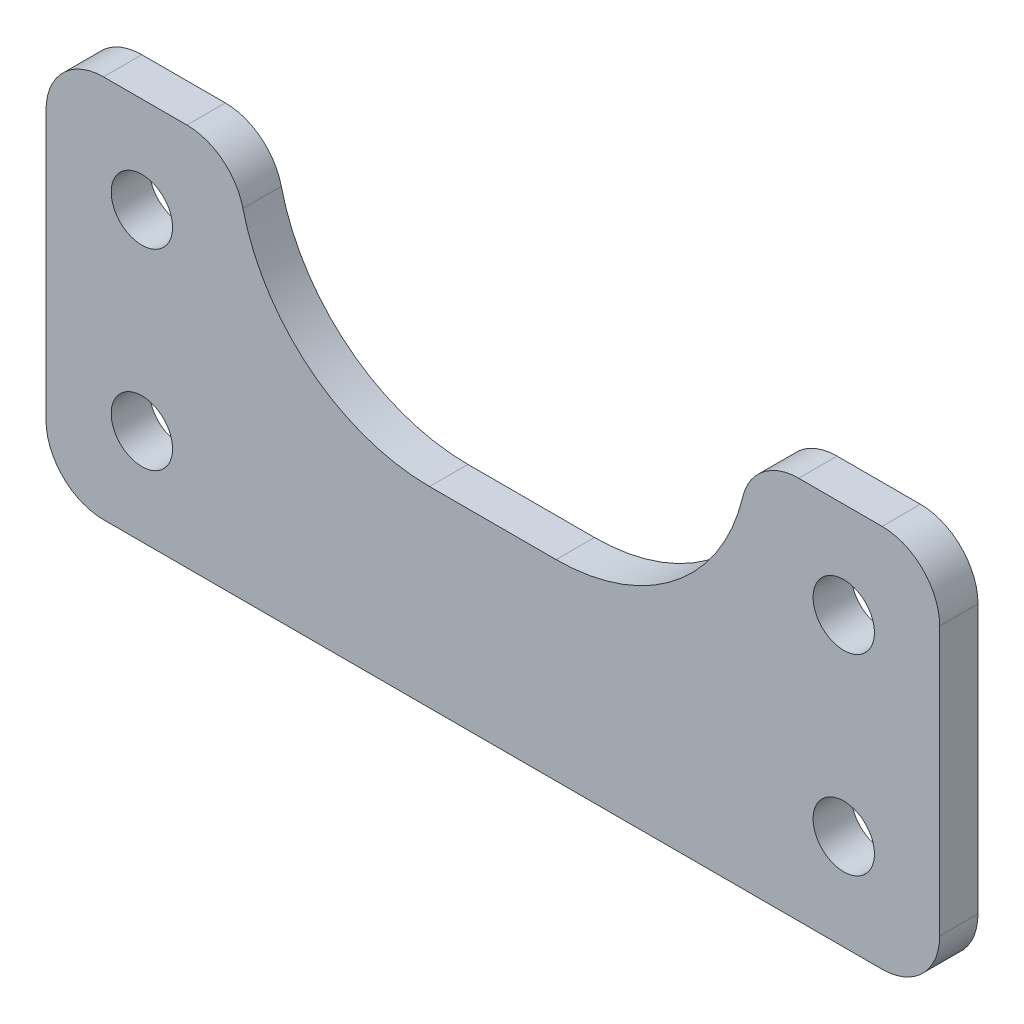
SolidWorks part; units mm, degrees
material "1060 合金"
ref_plane "正面" through (0, 0, 0) normal (0, 0, 1) x (1, 0, 0)
ref_plane "平面" through (0, 0, 0) normal (0, 1, 0) x (1, 0, 0)
ref_plane "右側面" through (0, 0, 0) normal (1, 0, 0) x (0, 0, -1)
sketch "ｽｹｯﾁ1" plane through (0, 0, 0) normal (0, 0, 1) x (1, 0, 0)
  line L0 (10, 10) -> (10, 0) construction
  line L1 (0, 0) -> (46.6, 0)
  line L2 (0, 0) -> (0, 20)
  line L3 (0, 20) -> (46.6, 20)
  line L4 (46.6, 0) -> (46.6, 20)
  line L5 (10, 20) -> (36.6, 20)
  line L6 (10, 20) -> (10, 10)
  line L7 (10, 10) -> (36.6, 10)
  line L8 (36.6, 20) -> (36.6, 10)
  line L9 (10, 5) -> (0, 5) construction
  line L10 (5, 5) -> (5, 20) construction
  line L11 (23.3, 10) -> (23.3, 0) construction
  circle A1 centre (5, 5) radius 1.6
  circle A2 centre (5, 15) radius 1.6
  circle A3 centre (41.6, 15) radius 1.6
  circle A4 centre (41.6, 5) radius 1.6
  dimension "D6" = 10
  dimension "D7" = 3.2
  dimension "D1" = 10
  dimension "D2" = 10
  dimension "D3" = 20
  dimension "D4" = 46.6
  dimension "D5" = 10
extrude "ﾎﾞｽ - 押し出し1" add sketch "ｽｹｯﾁ1" along normal blind 2 contours L3 L8 L7 L6 L2 L1 L4 A3 A2 A1 A4 region at (23.3, 7.9016, 0)
fillet "ﾌｨﾚｯﾄ1" radius 10 2 edges at (36.6, 10, 1) (10, 10, 1)
fillet "ﾌｨﾚｯﾄ2" radius 3 6 edges at (0, 0, 1) (46.6, 0, 1) (46.6, 20, 1) (36.6, 20, 1) (0, 20, 1) (10, 20, 1)
